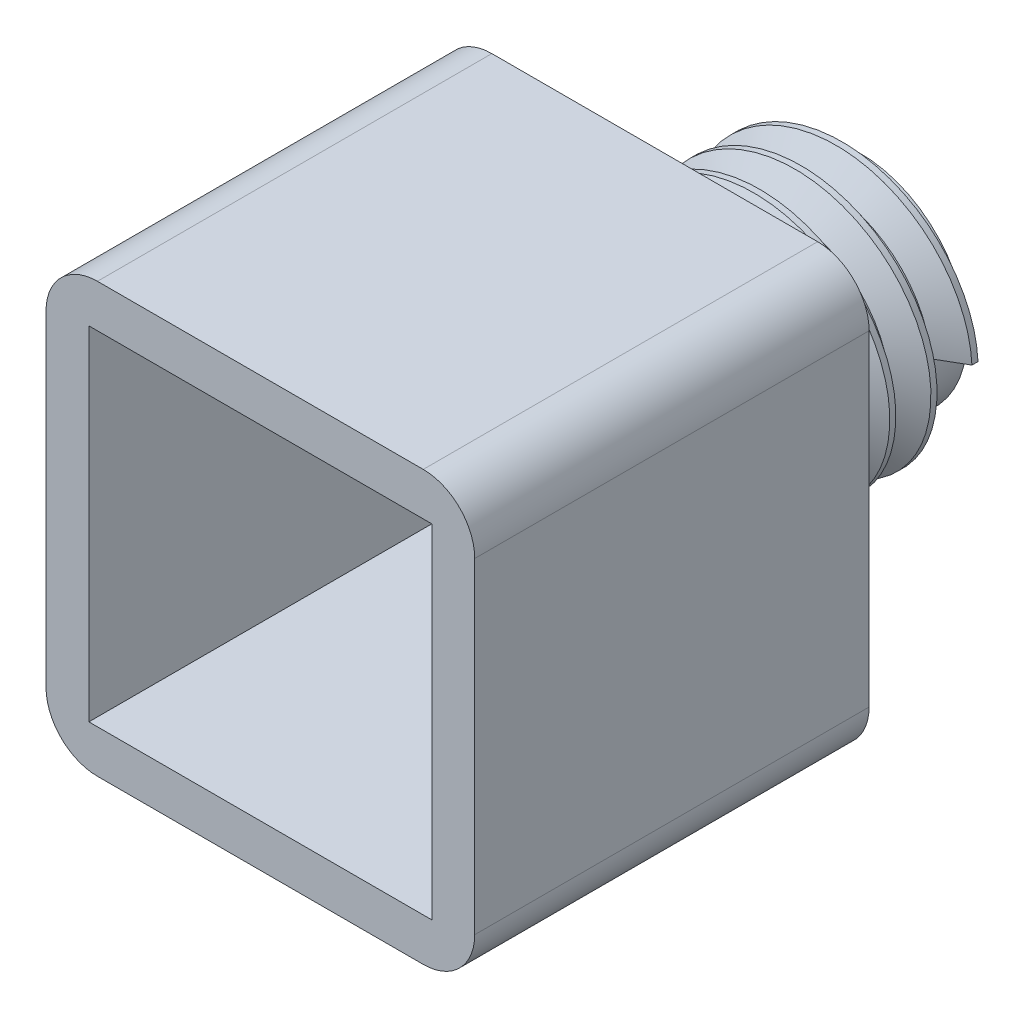
SolidWorks part; units mm, degrees
ref_plane "Front" through (0, 0, 0) normal (0, 0, 1) x (1, 0, 0)
ref_plane "Top" through (0, 0, 0) normal (0, 1, 0) x (1, 0, 0)
ref_plane "Right" through (0, 0, 0) normal (1, 0, 0) x (0, 0, -1)
sketch "草图1" plane through (0, 0, 0) normal (0, 0, 1) x (1, 0, 0)
  circle A0 centre (0, 0) radius 6.205
  dimension "D1" = 12.41
extrude "凸台-拉伸2" add sketch "草图1" along normal blind 20
thread "螺纹线2" pitch 2.8222 method extrude profile "螺纹线轮廓2" start angle 0, offset 0, length 0, pitch 2.4, diameter 12.41
ref_plane "基准面2" through (6.205, 0, 0) normal (0, -1, 0) x (1, 0, 0)
sketch "螺纹线轮廓2" plane through (6.205, 0, 0) normal (0, -1, 0) x (1, 0, 0)
  line L0 (0, 0) -> (0, 2.8222) construction
  line L1 (0, 0) -> (1.5276, 0.8819)
  line L2 (1.5276, 0.8819) -> (1.5276, 1.2347)
  line L3 (1.5276, 1.2347) -> (0, 2.1167)
  line L4 (1.5276, 1.0583) -> (0, 1.0583) construction
  line L11 (0, 0) -> (0, 2.1167)
  point P2 (0, 0)
  dimension "Pitch" = 2.8222
  dimension "Profile_Angle" = 60
  dimension "Profile_Land" = 0.3528
  dimension "Profile_Height" = 1.5276
sketch "草图53" plane through (0, 0, 20) normal (0, 0, 1) x (1, 0, 0)
  line L1 (-12.5, 12.5) -> (12.5, 12.5)
  line L2 (-12.5, 12.5) -> (-12.5, -12.5)
  line L3 (-12.5, -12.5) -> (12.5, -12.5)
  line L4 (12.5, 12.5) -> (12.5, -12.5)
  line L5 (-12.5, 12.5) -> (12.5, -12.5) construction
  line L6 (-12.5, -12.5) -> (12.5, 12.5) construction
  point P0 (0, 0)
  dimension "D1" = 25
  dimension "D2" = 25
extrude "凸台-拉伸3" add sketch "草图53" along normal blind 15 and the other way blind 8
fillet "圆角1" radius 5 1 edges at (6.205, 0, 12)
sketch "草图54" plane through (0, 0, 35) normal (0, 0, 1) x (1, 0, 0)
  line L1 (-10, 10) -> (10, 10)
  line L2 (-10, 10) -> (-10, -10)
  line L3 (-10, -10) -> (10, -10)
  line L4 (10, 10) -> (10, -10)
  line L5 (-10, 10) -> (10, -10) construction
  line L6 (-10, -10) -> (10, 10) construction
  point P0 (0, 0)
  dimension "D1" = 20
  dimension "D2" = 20
extrude "切除-拉伸2" cut sketch "草图54" against normal offset from surface (20 mm away) 3 up to face at (11.205, 0, 12)
fillet "圆角2" radius 3 4 edges at (12.5, -12.5, 23.5) (12.5, 12.5, 23.5) (-12.5, 12.5, 23.5) (-12.5, -12.5, 23.5)
